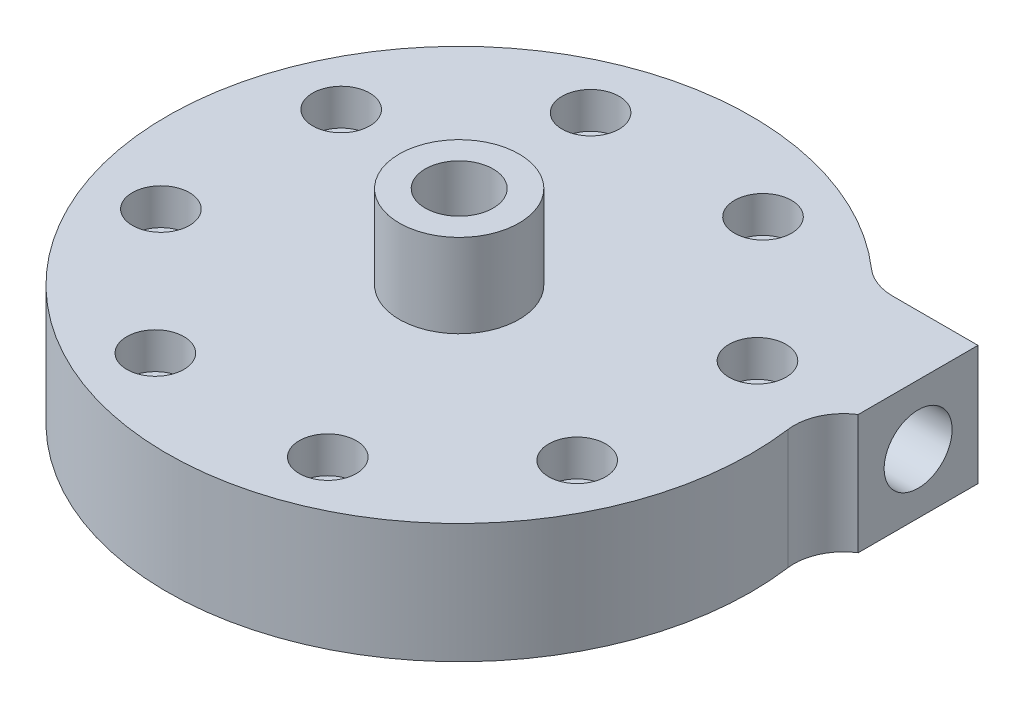
SolidWorks part; units mm, degrees
material "1060 Alloy"
ref_plane "Front" through (0, 0, 0) normal (0, 0, 1) x (1, 0, 0)
ref_plane "Top" through (0, 0, 0) normal (0, 1, 0) x (1, 0, 0)
ref_plane "Right" through (0, 0, 0) normal (1, 0, 0) x (0, 0, -1)
sketch "Sketch1" plane through (0, 0, 0) normal (0, 1, 0) x (1, 0, 0)
  line L0 (0, 0) -> (2.6731, 30.5538) construction
  line L1 (21.117, 30.6705) -> (50.1264, 33.2085) construction
  line L2 (11.6189, 28.3845) -> (50.1264, 28.3845) construction
  line L3 (21.117, 26.0945) -> (50.1264, 23.5565) construction
  line L4 (0, 0) -> (56.1418, -4.9118) construction
  line L5 (21.117, 30.6705) -> (21.117, 28.3845) construction
  line L6 (21.117, 28.3845) -> (21.117, 26.0945) construction
  line L7 (50.1264, 28.3845) -> (50.1264, 33.2085) construction
  line L8 (50.1264, 28.3845) -> (50.1264, 23.5565) construction
  line L9 (60.1264, 28.3845) -> (60.1264, 39.9329)
  line L10 (60.1264, 34.9329) -> (50.1264, 34.9329) construction
  line L11 (60.1264, 34.9329) -> (60.1264, 21.8361) construction
  line L12 (60.1264, 21.8361) -> (50.1264, 21.8361) construction
  line L13 (50.1264, 34.9329) -> (50.1264, 21.8361) construction
  line L14 (60.1264, 39.9329) -> (43.7019, 39.9329)
  line L15 (60.1264, 28.3845) -> (60.1264, 16.8361)
  line L17 (21.117, 30.6705) -> (0, 30.6705) construction
  line L18 (21.117, 26.0945) -> (16.117, 26.0945) construction
  arc A0 (37.1159, 42.408) -> (55.8478, 7.5534) centre (0, 0) ccw
  circle A1 centre (0, 0) radius 30.6705 construction
  arc A2 (55.8478, 7.5534) -> (60.1264, 16.8361) centre (65.2868, 8.8301) cw
  arc A3 (43.7019, 39.9329) -> (37.1159, 42.408) centre (43.7019, 49.9329) cw
  dimension "D1" = 112.7125
  dimension "D2" = 61.341
  dimension "D13" = 9.525
  dimension "D4" = 2.286
  dimension "D3" = 2.29
  dimension "D5" = 5
  dimension "D6" = 5
  dimension "D7" = 5
  dimension "D8" = 9.652
  dimension "D9" = 13.0969
  dimension "D10" = 10
  dimension "D11" = 5
  dimension "D14" = 5
  dimension "D12" = 5
extrude "main body" add sketch "Sketch1" along normal blind 23.0969
ref_plane "body midsection" through (0, 11.5484, 0) normal (0, 1, 0) x (1, 0, 0)
sketch "Sketch7" plane through (0, 23.0969, 0) normal (0, 1, 0) x (1, 0, 0)
  circle A0 centre (0, 0) radius 25.4
  dimension "D1" = 50.8
extrude "inlet boss" add sketch "Sketch7" along normal blind 50.8
sketch "Sketch3" plane through (0, 11.5484, 0) normal (0, 1, 0) x (1, 0, 0)
  line L0 (21.117, 30.6705) -> (0, 30.6705)
  line L1 (0, 30.6705) -> (0, 28.3845)
  line L2 (50.1264, 28.3845) -> (2.4833, 28.3845)
  line L3 (0, 0) -> (2.6731, 30.5538) construction
  line L4 (0, 28.3845) -> (2.4833, 28.3845)
  line L5 (50.1264, 33.2085) -> (50.1264, 34.9329)
  line L6 (50.1264, 34.9329) -> (60.1264, 34.9329)
  line L7 (60.1264, 34.9329) -> (60.1264, 28.3845)
  line L8 (60.1264, 28.3845) -> (50.1264, 28.3845)
  line L9 (21.117, 30.6705) -> (50.1264, 33.2085)
revolve "expansion cone and outlet" cut sketch "Sketch3" angle 360 about L2
sketch "Sketch2" plane through (0, 0, 0) normal (0, 0, 1) x (1, 0, 0)
  line L0 (-56.3562, 11.5484) -> (56.3562, 11.5484) construction
  line L1 (-56.3562, 23.0969) -> (-56.3562, 0) construction
  line L2 (56.3562, 0) -> (56.3562, 23.0969) construction
  line L3 (0, 0) -> (0, 23.0969) construction
  line L4 (25.4, 23.0969) -> (-25.4, 23.0969) construction
  line L5 (0, 18.6817) -> (0, 9.0936)
  line L6 (0, 9.0936) -> (26.67, 9.0936) construction
  line L7 (5.461, 18.6817) -> (5.565, 19.1708) construction
  line L8 (26.67, 14.1736) -> (5.461, 14.1736) construction
  line L9 (26.67, 9.0936) -> (26.67, 14.1736) construction
  line L10 (0, 19.1929) -> (0, 39.1929)
  line L11 (26.67, 14.1736) -> (5.461, 18.6817) construction
  line L12 (5.461, 18.6817) -> (0, 18.6817) construction
  line L13 (5.461, 18.6817) -> (5.461, 9.0936) construction
  line L14 (0, 9.0936) -> (0, 7.0936) construction
  line L15 (0, 7.0936) -> (26.67, 7.0936) construction
  line L16 (26.67, 7.0936) -> (26.67, 9.0936) construction
  line L17 (0, 9.0936) -> (0, 6.5936)
  line L18 (0, 7.0936) -> (0, 6.5936) construction
  line L19 (0, 6.5936) -> (26.67, 6.5936) construction
  line L20 (26.67, 6.5936) -> (26.67, 7.0936) construction
  line L21 (26.67, 6.5936) -> (30.6705, 6.5936) construction
  line L22 (30.6705, 6.5936) -> (30.6705, 13.3233)
  line L23 (26.67, 14.1736) -> (30.6705, 13.3233) construction
  line L24 (5.461, 18.6817) -> (5.461, 19.1929) construction
  line L25 (5.461, 19.1929) -> (0, 19.1929) construction
  line L26 (0, 19.1929) -> (0, 18.6817)
  line L27 (30.6705, 13.3233) -> (30.6705, 13.8344)
  line L28 (30.6705, 13.8344) -> (5.461, 19.1929)
  line L29 (0, 6.5936) -> (0, 0)
  line L30 (0, 0) -> (30.6705, 0)
  line L31 (-56.3562, 0) -> (56.3562, 0) construction
  line L32 (30.6705, 0) -> (30.6705, 6.5936)
  line L33 (30.6705, 13.8344) -> (0, 13.8344) construction
  line L34 (21.117, 13.8344) -> (0, 13.8344) construction
  line L35 (0, 39.1929) -> (6.5484, 39.1929) construction
  line L36 (6.5484, 39.1929) -> (6.5484, 29.1929)
  line L37 (6.5484, 29.1929) -> (5.461, 29.1929)
  line L38 (5.461, 29.1929) -> (5.461, 19.1929)
  line L39 (0, 39.1929) -> (0, 73.8969)
  line L40 (0, 73.8969) -> (25.4, 73.8969)
  line L41 (6.5484, 39.1929) -> (11.5484, 39.1929)
  line L42 (25.4, 73.8969) -> (-25.4, 73.8969) construction
  line L44 (11.5484, 39.1929) -> (11.5484, 23.0969)
  line L46 (25.4, 73.8969) -> (25.4, 23.0969)
  line L47 (25.4, 23.0969) -> (11.5484, 23.0969)
  dimension "D10" = 10
  dimension "D12" = 5
  dimension "D1" = 5.461
  dimension "D2" = 26.67
  dimension "D3" = 9.5881
  dimension "D4" = 5.08
  dimension "D5" = 2
  dimension "D6" = 4.0005
  dimension "D8" = 0.5
  dimension "D9" = 10
  dimension "D11" = 6.5484
revolve "main chamber" cut sketch "Sketch2" angle 360 about L5
sketch "Sketch5" plane through (0, 23.0969, 0) normal (0, 1, 0) x (1, 0, 0)
  line L1 (17.9206, 40.6775) -> (41.4351, 16.0915) construction
  line L3 (11.6189, 28.3845) -> (50.1264, 28.3845) construction
  circle A0 centre (0, 0) radius 44.45 construction
  circle A1 centre (41.4351, 16.0915) radius 2.9766
  circle A2 centre (0, 0) radius 44.45 construction
  circle A3 centre (40.6775, -17.9206) radius 2.9766
  circle A4 centre (0, 0) radius 44.45 construction
  circle A5 centre (16.0915, -41.4351) radius 2.9766
  circle A6 centre (0, 0) radius 44.45 construction
  circle A7 centre (-17.9206, -40.6775) radius 2.9766
  circle A8 centre (0, 0) radius 44.45 construction
  circle A9 centre (-41.4351, -16.0915) radius 2.9766
  circle A10 centre (0, 0) radius 44.45 construction
  circle A11 centre (-40.6775, 17.9206) radius 2.9766
  circle A12 centre (0, 0) radius 44.45 construction
  circle A13 centre (-16.0915, 41.4351) radius 2.9766
  circle A14 centre (0, 0) radius 44.45 construction
  circle A15 centre (17.9206, 40.6775) radius 2.9766
  point P5 (29.6778, 28.3845)
  point P30 (0, 0)
  dimension "D1" = 88.9
  dimension "D2" = 5.9531
  dimension "D4" = 8
sketch "Sketch6" plane through (0, 23.0969, 0) normal (0, 1, 0) x (1, 0, 0)
  circle A0 centre (41.4351, 16.0915) radius 5.5
  circle A1 centre (40.6775, -17.9206) radius 5.5
  circle A2 centre (16.0915, -41.4351) radius 5.5
  circle A3 centre (-17.9206, -40.6775) radius 5.5
  circle A4 centre (-41.4351, -16.0915) radius 5.5
  circle A5 centre (-40.6775, 17.9206) radius 5.5
  circle A6 centre (-16.0915, 41.4351) radius 5.5
  circle A7 centre (17.9206, 40.6775) radius 5.5
  point P19 (0, 0)
  dimension "D1" = 11
  dimension "D2" = 8
ref_plane "exit axial plane" through (0, 0, -28.3845) normal (0, 0, -1) x (-1, 0, 0)
extrude "bolt clearances" cut sketch "Sketch5" against normal through all
extrude "bolt head clearance" cut sketch "Sketch6" against normal blind 7
equation "\"bearing OD\" = 30mm"
equation "\"bearing ID\"= 10mm"
equation "\"bearing depth\"= 9mm"
equation "\"bearing outer race thickness\"= 1mm"
equation "\"bearing inner race thickness\"= 1mm"
equation "\"bearing bore\" = \"bearing depth\" + 1mm"
equation "\"z\" = 8\t\t\t\t'number of blades"
equation "\"de\" = 0.43in\t\t\t'entrance eye diameter"
equation "\"d2\" = 2.1in \t\t\t'outer diameter of the impeller"
equation "\"d_exit\" = 0.18in \t\t'throat aka d1"
equation "\"theta\" = 12\t\t\t'angle of blades from inner to outer "
equation "\"b2\" = .2in\t\t\t'tip height from disc surface at d2; slightly higher than d_exit"
equation "\"b1\" = \"b2\" + (\"d2\"/2 - \"de\"/2)*tan(\"theta\") \t\t\t'tip height from disc surface at inlet eye"
equation "\"s\"=\"ce\" - \"z\"*\"s_open\""
equation "\"impeller upper clearance\"= .5mm"
equation "\"impeller horizontal clearance\"= (\"d2\"*1.15 - \"d2\")/2 \t\t'clearance based on D2-D3 ratio for circular volute, ranges 1.15 to 1.2"
equation "\"impeller bottom clearance\"= .5mm"
equation "\"impeller base thickness\"= 2mm"
equation "\"impeller dowel diameter\" = 2mm"
equation "\"impeller bolt head diameter\" = \"m4 head bore diameter\""
equation "\"impeller bolt head depth\" = 4mm"
equation "\"impeller bolt stop depth\" = 3mm"
equation "\"impeller bolt bore\" = \"m4 clearance\""
equation "\"impeller shaft bore depth\" = 12mm"
equation "\"impeller shaft bore\" = 8mm"
equation "\"impeller boss depth\" = \"impeller shaft bore depth\"+\"impeller bolt stop depth\"+\"impeller bolt head depth\"-\"impeller base thickness\""
equation "\"impeller boss diameter\" = \"upper seal ID\""
equation "\"impeller dowel length\" = 2mm*2 + \"impeller shaft bore\""
equation "\"coupler motor shaft hole ID\"= 8mm"
equation "\"coupler OD\"= 17mm"
equation "\"coupler length\"= 25mm"
equation "\"motor OD\" = 64mm"
equation "\"motor shaft diameter\"= 8mm"
equation "\"motor shaft pride\"= 32mm"
equation "\"motor to bearing plate distance\" = \"motor shaft pride\" + 2mm +\"coupler length\"/2"
equation "\"square plate bolt bore\" = \"m8 clearance\""
equation "\"square plate bolt head diameter\" = 13.5mm"
equation "\"square plate bolt head depth\" = 8mm"
equation "\"square plate bolt pattern diameter\"= 3.5in"
equation "\"motor mount center bore\"= \"coupler OD\"+ 4mm"
equation "\"motor mount post radius\"= ( 3 * \"square plate bolt bore\" ) / 2"
equation "\"motor mount m4 screw hole diameter\"= 4mm"
equation "\"motor mount m4 head diameter\"= 7.25mm"
equation "\"motor mount m4 head depth\"= 4mm"
equation "\"motor mount m4 pattern diamater\" = 30mm"
equation "\"motor mount plate thickness\"= 8mm + \"motor mount m4 head depth\""
equation "\"bearing plate stop ID\" = \"bearing OD\" - 4mm"
equation "\"bearing plate stop depth\" = 3mm"
equation "\"bearing plate thickness\" = \"bearing bore\" + \"bearing plate stop depth\" + \"shaft bearing stop length\""
equation "\"shaft coupler section diameter\" = 8mm"
equation "\"shaft coupler section length\" = \"motor to bearing plate distance\" - \"motor shaft pride\" - 2mm"
equation "\"shaft bearing section diameter\" = \"bearing ID\""
equation "\"shaft bearing section length\" = \"bearing plate stop depth\" + \"bearing depth\""
equation "\"shaft bearing stop diameter\" = \"bearing ID\" + 4mm"
equation "\"shaft bearing stop length\" = 3mm"
equation "\"impeller cavity center height\"= \"impeller bottom clearance\" + \"impeller upper clearance\" + \"impeller center height\""
equation "\"impeller cavity diameter\"= 2 * \"impeller horizontal clearance\" + \"d2\" \t\t\t\t\t\t\t\t\t'called D3 analytically"
equation "\"impeller cavity outer height\"= \"impeller bottom clearance\" + \"impeller upper clearance\" + \"impeller base thickness\" + \"b2\" \t\t'this is height at impeller diameter d2, not at d3"
equation "\"impeller housing thickness\"= \"impeller housing exit threaded diameter\" + 2*\"impeller housing outlet grip\""
equation "\"impeller housing diameter\" = \"square plate bolt pattern diameter\" + 2*\"motor mount post radius\""
equation "\"impeller housing bolt count\" = 8"
equation "\"impeller housing bolt diameter\" = \"m6 clearance\""
equation "\"impeller housing bolt pattern diameter\" = 3.5in"
equation "\"impeller housing threaded inlet diameter\" = 0.515625in \t'this is the 33/64 drill size for 9/16-18 fitting, expecting swagelok SS-8FK0-1-6STH fitting"
equation "\"impeller housing threaded inlet depth\"= 10mm"
equation "\"impeller housing exit threaded diameter\"= 0.515625in \t\t'this is the 33/64 drill size for 9/16-18 fitting, expecting swagelok SS-8FK0-1-6STH fitting"
equation "\"impeller housing exit threaded depth\"= 10mm"
equation "\"impeller housing diffuser conical angle\"=10"
equation "\"impeller housing diffuser tangent angle\"=5"
equation "\"impeller housing diffuser final diameter\" = .38in\t\t'aka d2'"
equation "\"impeller housing outlet grip\" = 5mm"
equation "\"D1@Sketch1\"=\"impeller housing diameter\""
equation "\"D2@Sketch1\"=\"impeller cavity diameter\""
equation "\"D4@Sketch1\"=\"d_exit\"/2"
equation "\"D5@Sketch1\"=\"impeller housing diffuser tangent angle\""
equation "\"D6@Sketch1\"=\"impeller housing diffuser conical angle\"/2"
equation "\"D7@Sketch1\"=\"impeller housing diffuser conical angle\"/2"
equation "\"D8@Sketch1\"=\"impeller housing diffuser final diameter\""
equation "\"D9@Sketch1\"=\"impeller housing exit threaded diameter\""
equation "\"D10@Sketch1\"=\"impeller housing exit threaded depth\""
equation "\"D11@Sketch1\"=\"impeller housing outlet grip\""
equation "\"D1@main body\" = \"impeller housing thickness\""
equation "\"de_length\" = 10mm\t\t'entrance eye consistent length"
equation "\"D1@Sketch5\"=\"impeller housing bolt pattern diameter\""
equation "\"D2@Sketch5\"=\"m6 clearance\""
equation "\"end mill size\" = 0.375in\t'for 3/8 endmill"
equation "\"ae\" = 3.14*(\"de\"^2)/4\t\t'entrance eye area'"
equation "\"ce\" = 3.14*\"de\"\t\t'entrance eye circumference"
equation "\"av_ratio\" = .325\t\t'ratio of av/ae at N_s of 470, range is .275 to .375, .325 ideal. High ratio means bigger area means smaller blades"
equation "\"av\" = \"ae\"*\"av_ratio\"\t\t'area between just two blades"
equation "\"s_open\" = \"av\"/\"b1\"\t\t'width of open area"
equation "\"impeller center height\" = \"impeller base thickness\" + \"b1\"\t'impeller height at de"
equation "\"impeller outer height\" = \"impeller base thickness\" + \"b2\"\t'impeller height at de"
equation "\"shaft impeller section diameter\" = \"impeller shaft bore\""
equation "\"shaft impeller section length\" = \"upper seal plate thickness\" + \"upper seal plate riser\" + \"impeller bottom clearance\" + \"impeller base thickness\" - \"impeller bolt head depth\" - \"impeller bolt stop depth\""
equation "\"m6 clearance\" = 0.234375in\t'this is 15/64 bit = 5.95mm, could use 6mm bit, B bit for 6.04mm or 1/4 bit for 6.35mm"
equation "\"m6 tap\" = 5mm\t\t\t'5mm is appropriate, could use 13/64 or #5,6,7"
equation "\"m6 head bore diameter\" = 11mm\t\t"
equation "\"m6 head bore depth\" = 7mm\t'actual is 6mm"
equation "\"m8 clearance\" = 0.3125in\t'this is 5/16in for 7.93mm, could use 8mm, O,P, or 21/64"
equation "\"m8 tap\" = 0.265625in\t\t'this is 17/64 for 6.746875mm"
equation "\"m8 head bore diameter\" = 14mm"
equation "\"m8 head bore depth\" = 9mm\t'actual is 8mm"
equation "\"D1@Sketch6\"=\"m6 head bore diameter\""
equation "\"D1@bolt head clearance\" = \"m6 head bore depth\""
equation "\"lower seal OD\" = .917in\t\t'this is https://www.mcmaster.com/#9281k121/=174001b"
equation "\"lower seal ID\"= .375in"
equation "\"lower seal depth\" = .625in + .218in"
equation "\"lower seal bore\" = \"lower seal depth\" + 1mm"
equation "\"upper seal OD\" = 1.125in\t'this is https://www.mcmaster.com/#5154t33/=173zuau, needs to be visually inspected before machining!"
equation "\"upper seal ID\"= 0.625in"
equation "\"upper seal depth\"= .25in\t'aka height; these values need to be confirmed by inspection!! We may want to compress the height."
equation "\"upper seal bore\" = \"upper seal depth\" + 1mm"
equation "\"big o-ring thickness\" = .139in"
equation "\"big o-ring OD\" = 2.734in"
equation "\"big o-ring ID\" = 3.012in"
equation "\"big o-ring groove depth\" = \"big o-ring thickness\"*4/5"
equation "\"lower seal plate lip depth\" = 2mm"
equation "\"lower seal plate lip ID\" = \"lower seal OD\" - 3mm"
equation "\"lower seal plate thickness\" = \"lower seal plate lip depth\" + \"lower seal bore\""
equation "\"shaft lower seal section diameter\" = \"lower seal ID\""
equation "\"shaft lower seal section length\" = \"lower seal plate thickness\" + 1mm"
equation "\"upper seal plate thickness\" = \"upper seal plate pressure hole diameter\"+10mm"
equation "\"upper seal plate lip ID\" = \"upper seal OD\" - 3mm"
equation "\"upper seal plate riser\" = 6.59mm \t\t'this number needs to be read from the housing file"
equation "\"upper seal plate pressure hole diameter\" = .125in\t'this is 1/8 drill "
equation "\"upper seal plate pressure tap diameter\" = .328125in \t'this is 21/64 drill for a 1/8 ANPT tap"
equation "\"upper seal plate pressure tap grip\" = 5mm\t\t'this is the area around the tap so it doesn't crack"
equation "\"upper seal plate pressure tap depth\" = 12"
equation "\"m4 clearance\" = 0.171875in \t'this is 11/64 bit for 4.36mm"
equation "\"m4 tap\" = 0.125in\t\t'this is 1/8 bit for 3.17mm"
equation "\"m4 head bore diameter\" = 7.5mm"
equation "\"m4 head bore depth\" = 5mm\t'actual is ~4mm"
equation "\"D1@Sketch2\"=\"de\"/2"
equation "\"D3@Sketch2\"=\"b1\""
equation "\"D4@Sketch2\"=\"b2\""
equation "\"D2@Sketch2\"=\"d2\"/2"
equation "\"D5@Sketch2\"=\"impeller base thickness\""
equation "\"D6@Sketch2\"=\"impeller horizontal clearance\""
equation "\"D7@Sketch2\"=\"impeller bottom clearance\""
equation "\"D8@Sketch2\"=\"impeller upper clearance\""
equation "\"D9@Sketch2\"=\"de_length\""
equation "\"D10@Sketch2\"=\"impeller housing threaded inlet depth\""
equation "\"D11@Sketch2\"=\"impeller housing threaded inlet diameter\"/2"
equation "\"D12@Sketch2\"=\"impeller housing outlet grip\""
equation "\"min blade thickness\" = .15in"
equation "\"l_exit\"= 5mm\t\t\t'length of eye entrance"
equation "\"D12@Sketch1\"=\"impeller housing outlet grip\""
equation "\"D13@Sketch1\"=\"end mill size\""
